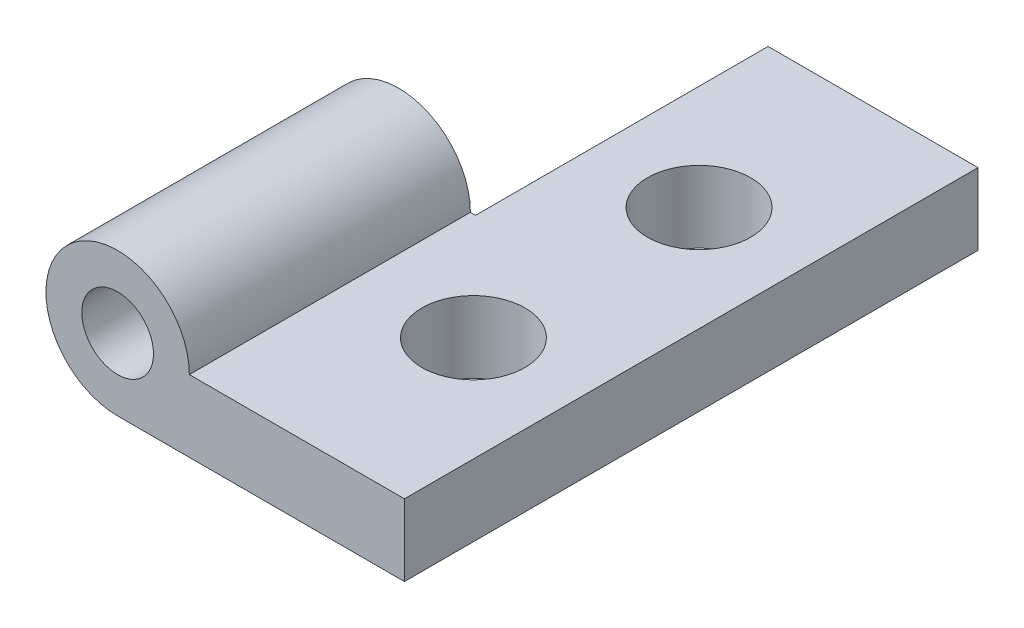
SolidWorks part; units mm, degrees
ref_plane "Front Plane" through (0, 0, 0) normal (0, 0, 1) x (1, 0, 0)
ref_plane "Top Plane" through (0, 0, 0) normal (0, 1, 0) x (1, 0, 0)
ref_plane "Right Plane" through (0, 0, 0) normal (1, 0, 0) x (0, 0, -1)
sketch "Sketch2" plane through (0, 0, 0) normal (0, 0, 1) x (1, 0, 0)
  line L1 (0, 0) -> (-12.7, 0)
  line L2 (0, 0) -> (0, 3.175)
  line L3 (0, 3.175) -> (-9.525, 3.175)
  arc A0 (-9.525, 3.175) -> (-12.7, 0) centre (-12.7, 3.175) ccw
  dimension "D1" = 12.7
  dimension "D2" = 3.175
extrude "Boss-Extrude1" add sketch "Sketch2" along normal blind 25.4
sketch "Sketch3" plane through (0, 0, 0) normal (0, 0, -1) x (-1, 0, 0)
  circle A1 centre (12.7048, 3.1942) radius 3.4093
extrude "Cut-Extrude1" cut sketch "Sketch3" against normal blind 12.954
sketch "Sketch4" plane through (0, 0, 12.954) normal (0, 0, -1) x (-1, 0, 0)
  circle A0 centre (13.0786, 6.3364) radius 0.009
  circle A2 centre (12.7, 3.175) radius 1.5875
  dimension "D1" = 3.175
extrude "Cut-Extrude2" cut sketch "Sketch4" against normal blind 12.954
sketch "Sketch5" plane through (0, 3.175, 0) normal (0, 1, 0) x (1, 0, 0)
  line L0 (-4.6478, -15.4093) -> (-4.6478, -9.9907) construction
  line L1 (-4.6478, -19.9813) -> (-4.6478, -25.4) construction
  line L2 (0, -25.4) -> (-9.525, -25.4) construction
  line L3 (-4.6478, -5.4187) -> (-4.6478, 0) construction
  line L4 (0, 0) -> (-9.2956, 0) construction
  line L5 (-6.9338, -7.7047) -> (-9.2956, -7.7047) construction
  line L6 (-9.2956, 0) -> (-9.2956, -12.954) construction
  line L7 (-2.3618, -7.7047) -> (0, -7.7047) construction
  line L8 (0, -25.4) -> (0, 0) construction
  circle A0 centre (-4.6478, -17.6953) radius 2.286
  circle A1 centre (-4.6478, -7.7047) radius 2.286
  dimension "D1" = 4.572
  dimension "D2" = 4.572
extrude "Cut-Extrude3" cut sketch "Sketch5" against normal blind 12.954
